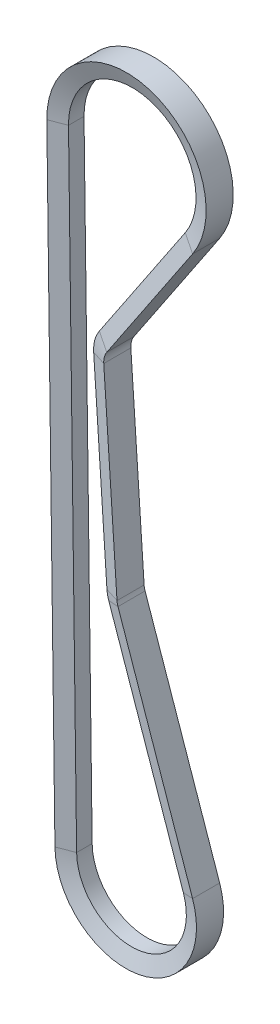
SolidWorks part; units mm, degrees
ref_plane "Front Plane" through (0, 0, 0) normal (0, 0, 1) x (1, 0, 0)
ref_plane "Top Plane" through (0, 0, 0) normal (0, 1, 0) x (1, 0, 0)
ref_plane "Right Plane" through (0, 0, 0) normal (1, 0, 0) x (0, 0, -1)
sketch "Sketch2" plane through (0, 0, 0) normal (0, 0, 1) x (1, 0, 0)
  line L0 (0, 0) -> (1, 0) construction
  line L1 (0, 0) -> (0, 1) construction
  line L12 (-24.8729, -0.3229) -> (-27.7282, 219.6364)
  line L14 (23.529, 204.4115) -> (-6.6534, 159.376)
  line L15 (-7.7144, 155.418) -> (-3.054, 85.5734)
  line L16 (-2.7189, 83.9195) -> (23.5072, 8.1349)
  arc A4 (-27.7282, 219.6364) -> (23.529, 204.4115) centre (0.2695, 219.9998) cw
  arc A7 (23.5072, 8.1349) -> (-24.8729, -0.3229) centre (0, 0) cw
  arc A8 (-6.6534, 159.376) -> (-7.7144, 155.418) centre (-1.3785, 155.8408) ccw
  arc A9 (-3.054, 85.5734) -> (-2.7189, 83.9195) centre (3.2819, 85.9961) ccw
ref_plane "Plane4" through (23.5072, 8.1349, 0) normal (0.327, -0.945, 0) x (-0.945, -0.327, 0)
sketch "Sketch3" plane through (23.5072, 8.1349, 0) normal (0.327, -0.945, 0) x (-0.945, -0.327, 0)
  line L0 (0, -4.7625) -> (0, 4.7625)
  line L1 (0, -4.7625) -> (5.588, -2.7286)
  line L2 (5.588, -2.7286) -> (5.588, 2.7286)
  line L3 (5.588, 2.7286) -> (0, 4.7625)
  line L4 (0, 0) -> (5.588, 0) construction
  dimension "D1" = 9.525
  dimension "D2" = 5.588
  dimension "D3" = 40
sweep "Sweep1" add profiles "Sketch3" path "Sketch2"
